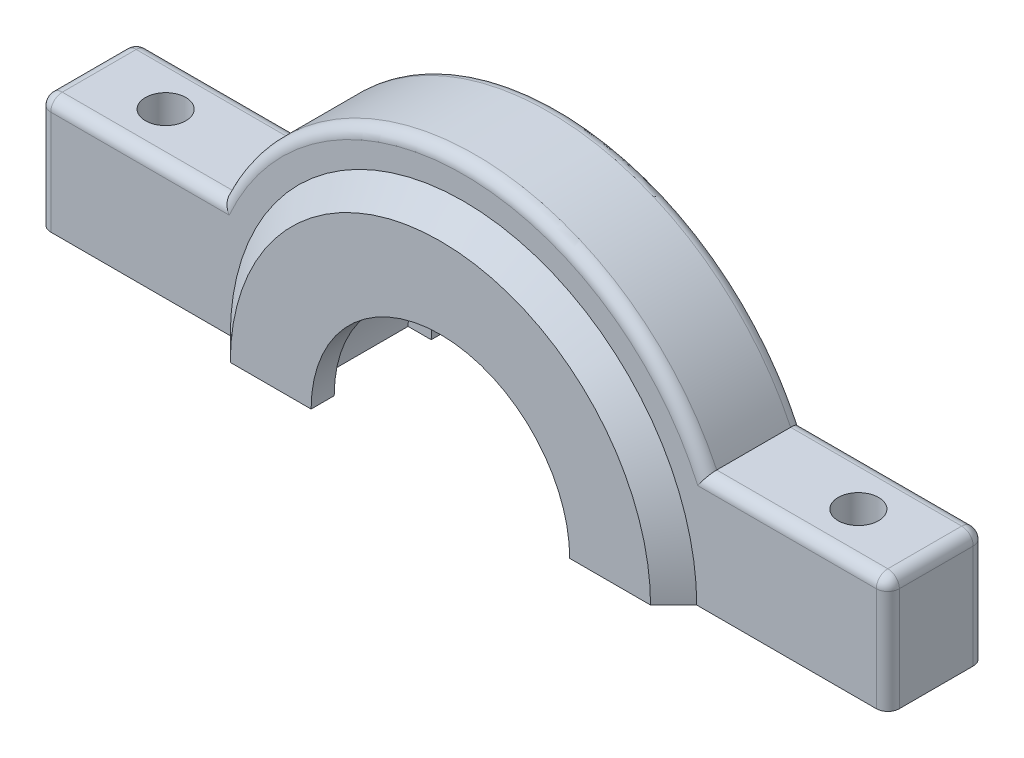
SolidWorks part; units mm, degrees
material "ABS"
ref_plane "Front Plane" through (0, 0, 0) normal (0, 0, 1) x (1, 0, 0)
ref_plane "Top Plane" through (0, 0, 0) normal (0, 1, 0) x (1, 0, 0)
ref_plane "Right Plane" through (0, 0, 0) normal (1, 0, 0) x (0, 0, -1)
sketch "Sketch1" plane through (0, 0, 0) normal (0, 0, 1) x (1, 0, 0)
  line L0 (36.75, 0) -> (13.2, 0)
  line L1 (-36.75, 0) -> (-36.75, 10)
  line L2 (-36.75, 10) -> (-20.9342, 10)
  line L3 (-36.75, 0) -> (-13.2, 0)
  line L4 (36.75, 0) -> (36.75, 10)
  line L5 (36.75, 10) -> (20.9342, 10)
  line L6 (0, 0) -> (0, 23.2) construction
  line L7 (30, 10) -> (30, 0) construction
  line L8 (-30, 10) -> (-30, 0) construction
  arc A0 (13.2, 0) -> (-13.2, 0) centre (0, 0) ccw
  arc A1 (20.9342, 10) -> (-20.9342, 10) centre (0, 0) ccw
  dimension "D3" = 13.2
  dimension "D1" = 10
  dimension "D2" = 10
  dimension "D4" = 6.75
  dimension "D5" = 6.75
  dimension "D6" = 60
extrude "Boss-Extrude1" add sketch "Sketch1" along normal mid plane 8.4
sketch "Sketch2" plane through (0, 0, 4.2) normal (0, 0, 1) x (1, 0, 0)
  line L0 (-18.2, 0) -> (-11.2, 0)
  line L1 (11.2, 0) -> (18.2, 0)
  arc A0 (11.2, 0) -> (-11.2, 0) centre (0, 0) ccw
  arc A1 (18.2, 0) -> (-18.2, 0) centre (0, 0) ccw
  arc A2 (13.2, 0) -> (-13.2, 0) centre (0, 0) ccw construction
  dimension "D1" = 2
  dimension "D2" = 5
extrude "Boss-Extrude2" add sketch "Sketch2" along normal blind 2
mirror "Mirror1" about plane through (0, 0, 0) normal (0, 0, 1) of "Boss-Extrude2"
chamfer "Chamfer1" distance 2 angle 45 2 edges at (0, 18.2, -4.2) (0, 18.2, 4.2)
sketch "Sketch3" plane through (0, 10, 0) normal (0, 1, 0) x (1, 0, 0)
  circle A0 centre (-30, 0) radius 1.75
  circle A1 centre (30, 0) radius 1.75
  point P0 (30, 0)
  point P2 (-30, 0)
  dimension "D1" = 3.5
extrude "Cut-Extrude1" cut sketch "Sketch3" against normal through all
fillet "Fillet1" radius 1 12 edges at (36.75, 5, 4.2) (36.75, 5, -4.2) (-36.75, 5, -4.2) (-36.75, 5, 4.2) (-36.75, 10, 0) (-28.8421, 10, -4.2) (0, 23.2, -4.2) (36.75, 10, 0) (28.8421, 10, -4.2) (28.8421, 10, 4.2) (0, 23.2, 4.2) (-28.8421, 10, 4.2)
equation "\"Bearing_OD\"= 26"
equation "\"Bearing_Thickness\"= 8"
equation "\"Screw_Hole_Diameter\"= 3.5"
equation "\"Screw_Hole_Distance\"= 60"
equation "\"Bearing_OD_Clearance\"= 0.4"
equation "\"Bearing_Thickness_Clearance\"= 0.4"
equation "\"Retainer_Thickness\"= 10"
equation "\"Retainer_Width\"= 8"
equation "\"Bearing_Lip_Width\"= 2"
equation "\"Bearing_Lip_Thickness\"= 2"
equation "\"D1@Sketch1\"=\"Retainer_Thickness\""
equation "\"D2@Sketch1\"=\"Retainer_Thickness\""
equation "\"D4@Sketch1\"=\"Screw_Hole_Diameter\" / 2 + 5"
equation "\"D5@Sketch1\"=\"Screw_Hole_Diameter\" / 2 + 5"
equation "\"D6@Sketch1\"=\"Screw_Hole_Distance\""
equation "\"D3@Sketch1\"=(\"Bearing_OD\" / 2) + (\"Bearing_OD_Clearance\"/2)"
equation "\"D1@Boss-Extrude1\"=\"Bearing_Thickness\" + \"Bearing_Thickness_Clearance\""
equation "\"D1@Sketch2\"=\"Bearing_Lip_Width\""
equation "\"D1@Boss-Extrude2\"=\"Bearing_Lip_Thickness\""
equation "\"D1@Chamfer1\"=\"Bearing_Lip_Thickness\""
equation "\"D1@Sketch3\"=\"Screw_Hole_Diameter\""
